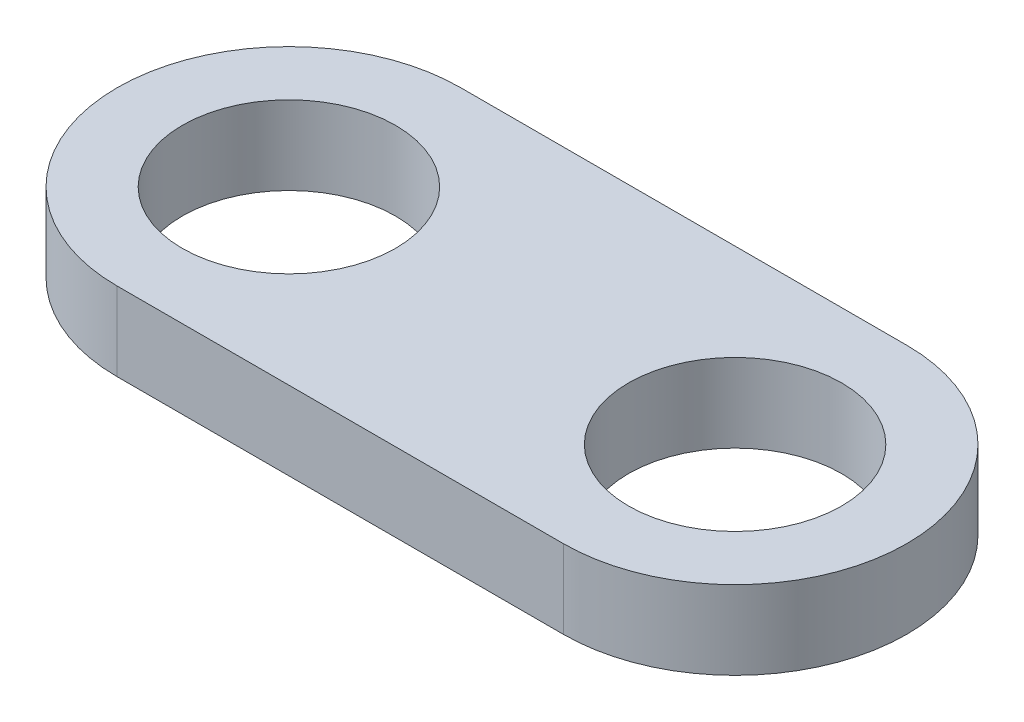
SolidWorks part; units mm, degrees
ref_plane "Front Plane" through (0, 0, 0) normal (0, 0, 1) x (1, 0, 0)
ref_plane "Top Plane" through (0, 0, 0) normal (0, 1, 0) x (1, 0, 0)
ref_plane "Right Plane" through (0, 0, 0) normal (1, 0, 0) x (0, 0, -1)
sketch "Sketch1" plane through (0, 0, 0) normal (0, 1, 0) x (1, 0, 0)
  line L0 (19.8792, 0) -> (-19.8792, 0)
  line L1 (-19.8792, -30.6106) -> (19.8792, -30.6106)
  arc A0 (-19.8792, 0) -> (-19.8792, -30.6106) centre (-19.8792, -15.3053) ccw
  arc A1 (19.8792, -30.6106) -> (19.8792, 0) centre (19.8792, -15.3053) ccw
  point P4 (0, 0)
  dimension "D1" = 39.7583
  dimension "D2" = 30.6106
extrude "Boss-Extrude1" add sketch "Sketch1" along normal blind 7
sketch "Sketch2" plane through (0, 7, 0) normal (0, 1, 0) x (1, 0, 0)
  line L0 (-19.8792, 0) -> (-19.8792, -30.6106) construction
  line L1 (0, 0) -> (0, -30.6106) construction
  line L2 (-19.8792, -30.6106) -> (19.8792, -30.6106) construction
  circle A0 centre (-19.8792, -15.3053) radius 9.5
  circle A2 centre (19.8792, -15.3053) radius 9.5
  dimension "D1" = 19
extrude "Cut-Extrude1" cut sketch "Sketch2" against normal through all
